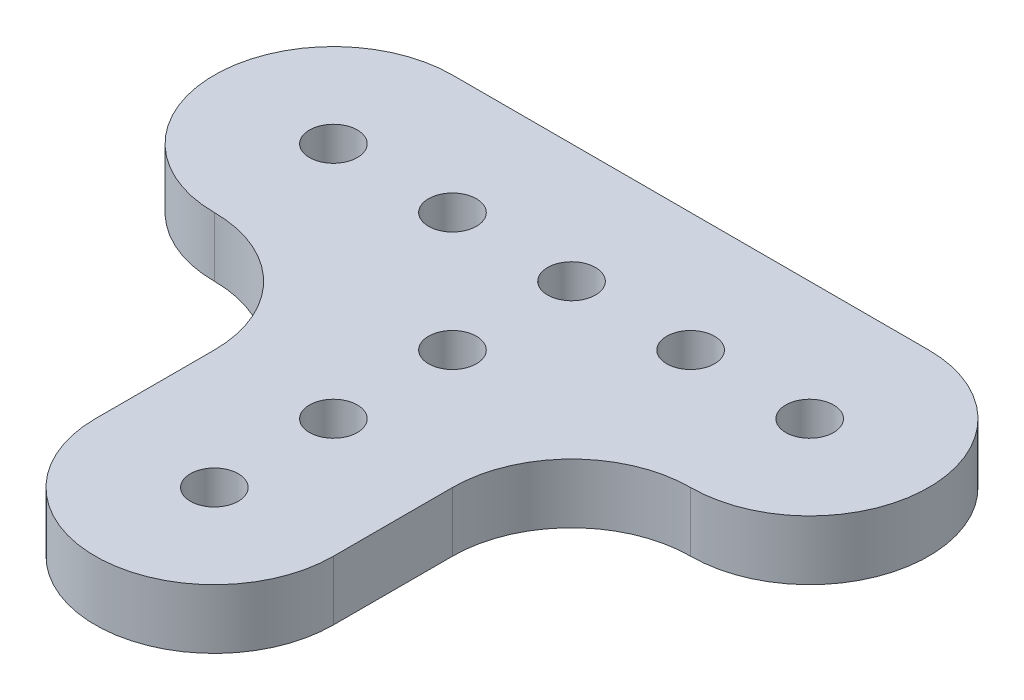
SolidWorks part; units mm, degrees
material "Birch Plywood"
ref_plane "Front Plane" through (0, 0, 0) normal (0, 0, 1) x (1, 0, 0)
ref_plane "Top Plane" through (0, 0, 0) normal (0, 1, 0) x (1, 0, 0)
ref_plane "Right Plane" through (0, 0, 0) normal (1, 0, 0) x (0, 0, -1)
sketch "Sketch1" plane through (0, 0, 0) normal (0, 1, 0) x (1, 0, 0)
  line L0 (0, 0) -> (12.7, 0) construction
  line L1 (25.4, 0) -> (25.4, -12.7) construction
  line L2 (0, 0) -> (50.8, 0) construction
  line L3 (0, 12.7) -> (50.8, 12.7)
  line L4 (0, -12.7) -> (50.8, -12.7)
  line L5 (25.4, -38.1) -> (25.4, 0) construction
  line L6 (12.7, -38.1) -> (12.7, 0)
  line L7 (38.1, -38.1) -> (38.1, 0)
  circle A0 centre (0, 0) radius 2.5527
  circle A1 centre (12.7, 0) radius 2.5527
  circle A2 centre (25.4, 0) radius 2.5527
  circle A3 centre (38.1, 0) radius 2.5527
  circle A4 centre (50.8, 0) radius 2.5527
  circle A5 centre (25.4, -12.7) radius 2.5527
  circle A6 centre (25.4, -25.4) radius 2.5527
  circle A7 centre (25.4, -38.1) radius 2.5527
  arc A9 (0, 12.7) -> (0, -12.7) centre (0, 0) ccw
  arc A10 (50.8, -12.7) -> (50.8, 12.7) centre (50.8, 0) ccw
  arc A11 (12.7, -38.1) -> (38.1, -38.1) centre (25.4, -38.1) ccw
  arc A12 (38.1, 0) -> (12.7, 0) centre (25.4, 0) ccw
  point P3 (25.4, 0)
  point P27 (25.4, -19.05)
  dimension "D1" = 5.1054
  dimension "D6" = 12.7
  dimension "D3" = 12.7
  dimension "D5" = 12.7
  dimension "D2" = 5
  dimension "D4" = 4
extrude "Boss-Extrude1" add sketch "Sketch1" along normal mid plane 6.35 contours A12 L3 A9 L4 L6 A1 A0 | A3 A12 A1 L6 L4 A5 L7 A2 | A12 A3 L7 L4 A10 L3 A4 | L6 A11 L7 L4 A5 A6 A7 region at (12.7, 0, -12.2421) region at (38.1, 0, -12.2421) region at (33.2051, 0, -9.5591) region at (25.4, 0, 30.6424)
fillet "Fillet1" radius 12.7 2 edges at (12.7, 0, 12.7) (38.1, 0, 12.7)
